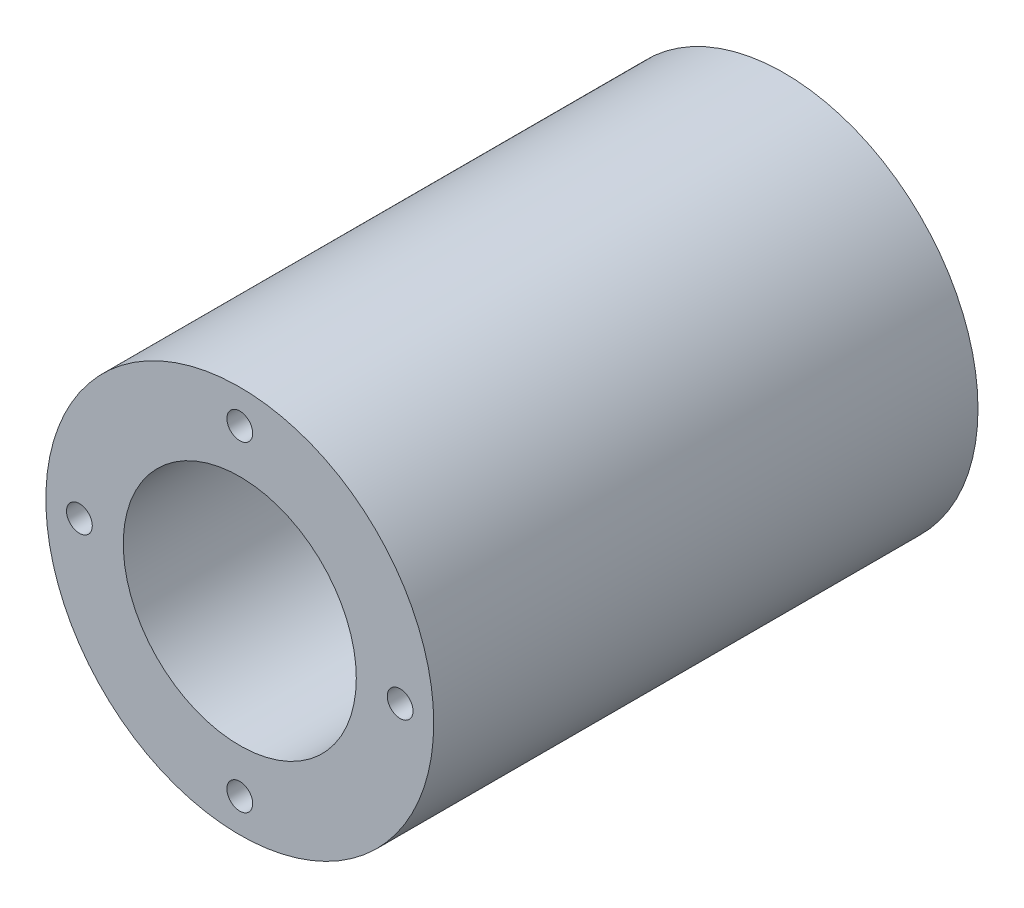
SolidWorks part; units mm, degrees
material "6061-T6 (SS)"
ref_plane "Front Plane" through (0, 0, 0) normal (0, 0, 1) x (1, 0, 0)
ref_plane "Top Plane" through (0, 0, 0) normal (0, 1, 0) x (1, 0, 0)
ref_plane "Right Plane" through (0, 0, 0) normal (1, 0, 0) x (0, 0, -1)
sketch "Sketch Spindle Skeleton" plane through (0, 0, 0) normal (1, 0, 0) x (0, 0, -1)
  line L0 (-103, -9.5) -> (-149, -9.5)
  line L5 (-1000, 0) -> (49000, 0)
  line L6 (0, -9.5) -> (0, 9.5)
  line L13 (0, 9.5) -> (-46.4, 9.5)
  line L26 (-46.4, 9.5) -> (-46.4, 14)
  line L27 (-46.4, 14) -> (-103, 14)
  line L32 (-103, 14) -> (-103, 9.5)
  line L34 (-165, 7) -> (-165, -7)
  line L36 (-103, -9.5) -> (-103, -14)
  line L37 (-103, -14) -> (-46.4, -14)
  line L38 (-46.4, -14) -> (-46.4, -9.5)
  line L39 (0, -9.5) -> (-46.4, -9.5)
  line L40 (-24.625, 37.6491) -> (-15.625, 37.6491)
  line L41 (-119.6, 22.6187) -> (-103, 22.6187)
  line L42 (-119.6, 22.6187) -> (-119.6, -22.6187)
  line L43 (-119.6, -22.6187) -> (-103, -22.6187)
  line L44 (-103, 22.6187) -> (-103, -22.6187)
  line L45 (-119.6, 22.6187) -> (-103, -22.6187) construction
  line L46 (-119.6, -22.6187) -> (-103, 22.6187) construction
  line L47 (-29.8, 22.6187) -> (-46.4, 22.6187)
  line L48 (-29.8, 22.6187) -> (-29.8, -22.6187)
  line L49 (-29.8, -22.6187) -> (-46.4, -22.6187)
  line L50 (-46.4, 22.6187) -> (-46.4, -22.6187)
  line L51 (-29.8, 22.6187) -> (-46.4, -22.6187) construction
  line L52 (-29.8, -22.6187) -> (-46.4, 22.6187) construction
  line L59 (-15.625, 37.6491) -> (-15.625, -37.6491)
  line L60 (-15.625, -37.6491) -> (-24.625, -37.6491)
  line L61 (-24.625, -22.6187) -> (-26.625, -22.6187)
  line L62 (-26.625, -22.6187) -> (-26.625, -12.5)
  line L63 (-26.625, -12.5) -> (-24.625, -12.5)
  line L64 (-24.625, -12.5) -> (-24.625, 12.5)
  line L65 (-24.625, 12.5) -> (-26.625, 12.5)
  line L66 (-26.625, 12.5) -> (-26.625, 22.6187)
  line L67 (-26.625, 22.6187) -> (-24.625, 22.6187)
  line L68 (-24.625, 22.6187) -> (-24.625, 37.6491)
  line L69 (-24.625, -22.6187) -> (-24.625, -37.6491)
  line L71 (-131.284, 37.6491) -> (-25.625, 37.6491)
  line L72 (-131.284, 37.6491) -> (-131.284, -37.6491)
  line L73 (-131.284, -37.6491) -> (-25.625, -37.6491)
  line L74 (-25.625, 37.6491) -> (-25.625, -37.6491)
  line L75 (-131.284, 37.6491) -> (-25.625, -37.6491) construction
  line L76 (-131.284, -37.6491) -> (-25.625, 37.6491) construction
  line L77 (-149, -9.5) -> (-149, -7)
  line L78 (-149, -7) -> (-165, -7)
  line L79 (-103, 9.5) -> (-149, 9.5)
  line L80 (-149, 7) -> (-165, 7)
  line L81 (-149, 9.5) -> (-149, 7)
  line L82 (-126, 9.5) -> (-126, -9.5) construction
  line L83 (-23.2, 9.5) -> (-23.2, -9.5) construction
  line L96 (-131.284, 37.6491) -> (-140.284, 37.6491)
  line L98 (-131.284, -37.6491) -> (-140.284, -37.6491)
  line L99 (-140.284, 37.6491) -> (-140.284, -37.6491)
  line L110 (-131.284, 37.6491) -> (-131.284, -37.6491)
  point P3 (0, 0)
  point P18 (-111.3, 0)
  point P24 (-38.1, 0)
  point P29 (-78.4545, 0)
  point P48 (-15.625, 31.1339)
  point P70 (-140.284, 31.1339)
sketch "Sketch1" plane through (0, 0, 0) normal (1, 0, 0) x (0, 0, -1)
  line L0 (-25.625, 37.6491) -> (-25.625, -37.6491) construction
  line L1 (-131.284, -37.6491) -> (-25.625, -37.6491) construction
  line L2 (-131.284, 37.6491) -> (-131.284, -37.6491) construction
  line L3 (-131.284, 37.6491) -> (-25.625, 37.6491) construction
  line L4 (-25.625, 37.6491) -> (-25.625, -37.6491)
  line L5 (-131.284, -37.6491) -> (-25.625, -37.6491)
  line L6 (-131.284, 37.6491) -> (-131.284, -37.6491)
  line L7 (-131.284, 37.6491) -> (-25.625, 37.6491)
  line L9 (-29.8, 22.6187) -> (-46.4, 22.6187) construction
  line L10 (-131.284, 22.6187) -> (-25.625, 22.6187)
  line L15 (-131.284, 0) -> (-25.625, 0) construction
revolve "Revolve1" add sketch "Sketch1" angle 360 about L15 region at (0, 30.1339, 78.4545)
sketch "Back Hole Top Location" plane through (0, 0, 25.625) normal (0, 0, -1) x (-1, 0, 0)
  point P9 (0, 31.1339)
hole_wizard "M6x1.0 Tapped Hole3" positions "Sketch8" profile "Sketch9" tap size "M6x1.0" standard "ANSI Metric"
sketch "Sketch8" plane through (0, 0, 25.625) normal (0, 0, -1) x (-1, 0, 0)
  point P0 (0, 31.1339)
sketch "Sketch9" plane through (0, 31.1339, 25.625) normal (1, 0, 0) x (0, 1, 0)
  line L0 (0, 0) -> (0, 16.5022)
  line L1 (0, 16.5022) -> (2.5, 15)
  line L2 (2.5, 15) -> (2.5, 0)
  line L5 (2.5, 0) -> (0, 0)
  line L10 (0, 16.5022) -> (-2.5, 15) construction
  line L11 (0, -6.35) -> (0, 107.95) construction
  dimension "Tap Drill Dia." = 5
  dimension "Tap Drill Depth" = 15
  dimension "Drill Angle" = 118
pattern_circular "BackFacePattern" count 6 over 360 about axis through (0, 0, 1000) along (0, 0, -1) of "M6x1.0 Tapped Hole3"
ref_plane "Midplane" through (0, 0, 78.4545) normal (0, 0, -1) x (-1, 0, 0)
sketch "Front Hole Top Location" plane through (0, 0, 131.284) normal (0, 0, 1) x (1, 0, 0)
  point P0 (0, 31.1339)
hole_wizard "M6x1.0 Tapped Hole2" positions "Sketch5" profile "Sketch6" tap size "M6x1.0" standard "ANSI Metric"
sketch "Sketch5" plane through (0, 0, 131.284) normal (0, 0, 1) x (1, 0, 0)
  point P0 (0, 31.1339)
sketch "Sketch6" plane through (0, 31.1339, 131.284) normal (1, 0, 0) x (0, -1, 0)
  line L0 (0, 0) -> (0, 16.5022)
  line L1 (0, 16.5022) -> (2.5, 15)
  line L2 (2.5, 15) -> (2.5, 0)
  line L5 (2.5, 0) -> (0, 0)
  line L10 (0, 16.5022) -> (-2.5, 15) construction
  line L11 (0, -6.35) -> (0, 107.95) construction
  dimension "Tap Drill Dia." = 5
  dimension "Tap Drill Depth" = 15
  dimension "Drill Angle" = 118
pattern_circular "FrontFacePattern" count 4 over 360 about axis through (0, 0, 1000) along (0, 0, -1) of "M6x1.0 Tapped Hole2"
sketch "Sketch7" plane through (0, 0, 25.625) normal (0, 0, -1) x (-1, 0, 0)
  circle A0 centre (0, 0) radius 26.9875
  circle A1 centre (0, 0) radius 24.6062
  dimension "D1" = 53.975
  dimension "D2" = 49.2125
extrude "Cut-Extrude1" cut sketch "Sketch7" against normal blind 0.5
